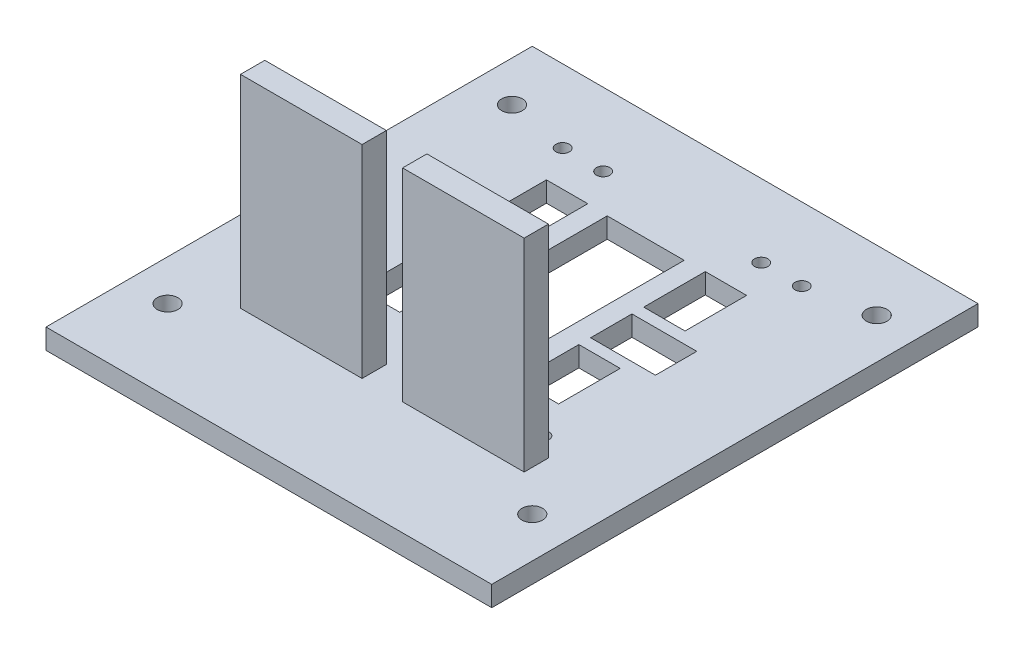
SolidWorks part; units mm, degrees
ref_plane "Front Plane" through (0, 0, 0) normal (0, 0, 1) x (1, 0, 0)
ref_plane "Top Plane" through (0, 0, 0) normal (0, 1, 0) x (1, 0, 0)
ref_plane "Right Plane" through (0, 0, 0) normal (1, 0, 0) x (0, 0, -1)
sketch "Sketch1" plane through (0, 0, 0) normal (0, 1, 0) x (1, 0, 0)
  line L0 (0, 0) -> (9.5, 0) construction
  line L1 (-55, 70) -> (55, 70)
  line L2 (-55, 70) -> (-55, -70)
  line L3 (-55, -70) -> (55, -70)
  line L4 (55, 70) -> (55, -70)
  line L5 (-55, 70) -> (55, -70) construction
  line L6 (-55, -70) -> (55, 70) construction
  line L7 (-9.5, 23) -> (9.5, 23)
  line L8 (-9.5, 23) -> (-9.5, -23)
  line L9 (-9.5, -23) -> (9.5, -23)
  line L10 (9.5, 23) -> (9.5, -23)
  line L11 (-9.5, 23) -> (9.5, -23) construction
  line L12 (-9.5, -23) -> (9.5, 23) construction
  line L14 (0, 0) -> (0, 35.7746) construction
  line L17 (-55, -70) -> (-20, -70)
  line L18 (-55, -70) -> (-55, -31.75)
  line L22 (-55, 70) -> (55, 70)
  line L23 (-55, 70) -> (-55, 50)
  line L24 (-55, 50) -> (55, 50)
  line L25 (55, 70) -> (55, 50)
  line L31 (-55, 31.75) -> (-55, -31.75)
  line L35 (55, 31.75) -> (55, -31.75)
  line L36 (-20, 70) -> (20, 70)
  line L40 (-20, -70) -> (20, -70)
  line L46 (2.5, -70) -> (42.5, -70)
  circle A1 centre (29.5, 32) radius 1.65
  circle A2 centre (19.5, 32) radius 1.65
  circle A3 centre (19.5, -32) radius 1.65
  circle A4 centre (29.5, -32) radius 1.65
  circle A5 centre (-29.5, -32) radius 1.65
  circle A6 centre (-19.5, -32) radius 1.65
  circle A7 centre (-19.5, 32) radius 1.65
  circle A8 centre (-29.5, 32) radius 1.65
  point P0 (0, 0)
  point P6 (0, 0)
  point P13 (0, 0)
  dimension "D5" = 9
  dimension "D8" = 20
  dimension "D9" = 20
  dimension "D6" = 3.3
  dimension "D1" = 140
  dimension "D2" = 110
  dimension "D3" = 46
  dimension "D4" = 19
  dimension "D7" = 2
extrude "Boss-Extrude3" add sketch "Sketch1" along normal blind 5 contours L4 L1 L2 L3 A7 A6 A5 A3 A2 A1 L7 L10 L9 L8 A4 A8 region at (0, 0, -48.3721)
sketch "Sketch5" plane through (0, 0, 0) normal (0, -1, 0) x (1, 0, 0)
  line L0 (-55, 70) -> (55, 70) construction
  line L1 (-55, -50) -> (-55, 70) construction
  line L2 (-55, -50) -> (55, -50) construction
  line L3 (0, 0) -> (0, -67.3907) construction
  circle A0 centre (-45, 50) radius 2.55
  circle A1 centre (-45, -35) radius 2.55
  circle A2 centre (45, -35) radius 2.55
  circle A3 centre (45, 50) radius 2.55
  dimension "D1" = 5.1
  dimension "D3" = 10
  dimension "D4" = 5.1
  dimension "D6" = 10
  dimension "D2" = 20
  dimension "D5" = 15
extrude "Cut-Extrude2" cut sketch "Sketch5" against normal through all
sketch "Sketch9" plane through (0, 5, 0) normal (0, 1, 0) x (1, 0, 0)
  line L0 (0, 0) -> (0, -16.1548) construction
  line L1 (-9.5, 23) -> (9.5, 23)
  line L2 (-9.5, 23) -> (-9.5, -23)
  line L3 (-9.5, -23) -> (9.5, -23)
  line L4 (9.5, 23) -> (9.5, -23)
  line L5 (-9.5, 23) -> (9.5, -23) construction
  line L6 (-9.5, -23) -> (9.5, 23) construction
  line L7 (-14.5, 23.2) -> (-24.7, 23.2)
  line L8 (-14.5, 23.2) -> (-14.5, -23.2)
  line L9 (-14.5, -23.2) -> (-24.7, -23.2)
  line L10 (-24.7, 23.2) -> (-24.7, -23.2)
  line L11 (-24.7, 8) -> (-14.5, 8)
  line L12 (-24.7, -8) -> (-14.5, -8)
  line L13 (24.7, -8) -> (14.5, -8)
  line L14 (24.7, 8) -> (14.5, 8)
  line L15 (24.7, 23.2) -> (24.7, -23.2)
  line L16 (14.5, -23.2) -> (24.7, -23.2)
  line L17 (14.5, 23.2) -> (14.5, -23.2)
  line L18 (14.5, 23.2) -> (24.7, 23.2)
  point P0 (0, 0)
  dimension "D1" = 5
  dimension "D2" = 10.2
  dimension "D3" = 0.2
  dimension "D4" = 0.2
  dimension "D5" = 15.2
  dimension "D6" = 15.2
extrude "Cut-Extrude3" cut sketch "Sketch9" against normal through all contours L10 L11 L8 L7 | L12 L10 L9 L8 | L13 L17 L16 L15 | L18 L17 L14 L15 region at (-19.6, 5, -15.6) region at (-19.6, 5, 15.6) region at (19.6, 5, 15.6) region at (19.6, 5, -15.6)
sketch "Sketch6" plane through (0, 5, 0) normal (0, 1, 0) x (1, 0, 0)
  line L6 (-9.5, -23) -> (9.5, -23) construction
  line L8 (-35, -36) -> (35, -36)
  line L9 (-35, -36) -> (-35, -42)
  line L10 (-35, -42) -> (35, -42)
  line L11 (35, -36) -> (35, -42)
  line L14 (-9.5, 23) -> (-9.5, -23) construction
  line L15 (5, -36) -> (-5, -36)
  line L16 (5, -36) -> (5, -42)
  line L17 (5, -42) -> (-5, -42)
  line L18 (-5, -36) -> (-5, -42)
  line L19 (9.5, 23) -> (9.5, -23) construction
  dimension "D1" = 13
  dimension "D2" = 6
  dimension "D3" = 4.5
  dimension "D4" = 4.5
  dimension "D5" = 30
  dimension "D6" = 30
extrude "Boss-Extrude4" add sketch "Sketch6" along normal blind 50 contours L18 L8 L9 L10 | L8 L16 L10 L11 region at (-20, 5, 39) region at (20, 5, 39)
sketch "Sketch11" plane through (0, 5, 0) normal (0, 1, 0) x (1, 0, 0)
  line L0 (9.5, 23) -> (9.5, -23) construction
  line L1 (14.5, 5.1) -> (30.5, 5.1)
  line L2 (14.5, 5.1) -> (14.5, -5.1)
  line L3 (14.5, -5.1) -> (30.5, -5.1)
  line L4 (30.5, 5.1) -> (30.5, -5.1)
  line L5 (-9.5, -23) -> (9.5, -23) construction
  line L6 (-9.5, 23) -> (9.5, 23) construction
  dimension "D1" = 5
  dimension "D2" = 16
  dimension "D3" = 17.9
  dimension "D4" = 17.9
extrude "Cut-Extrude4" cut sketch "Sketch11" against normal through all
